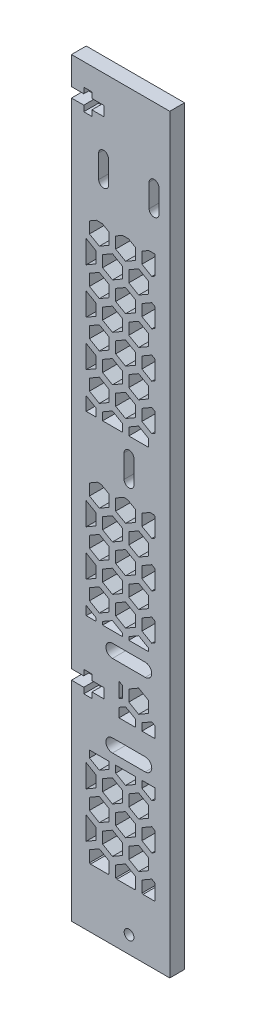
SolidWorks part; units mm, degrees
ref_plane "Front Plane" through (0, 0, 0) normal (0, 0, 1) x (1, 0, 0)
ref_plane "Top Plane" through (0, 0, 0) normal (0, 1, 0) x (1, 0, 0)
ref_plane "Right Plane" through (0, 0, 0) normal (1, 0, 0) x (0, 0, -1)
sketch "Sketch1" plane through (0, 0, 0) normal (0, 0, 1) x (1, 0, 0)
  line B0 (0, 114.5304) -> (25, 114.5304)
  line B1 (0, 114.5304) -> (0, -114.5304)
  line B2 (0, -114.5304) -> (25, -114.5304)
  line B3 (25, 114.5304) -> (25, -114.5304)
  line B4 (3.3, 89.1304) -> (0, 89.1304) construction
  line B5 (21.7, 89.1304) -> (25, 89.1304) construction
  line B6 (0, -100.1081) -> (25, -100.1081) construction
  circle B7 centre (4.8, 89.1304) radius 1.5
  circle B8 centre (20.2, 89.1304) radius 1.5
  circle B9 centre (12.5588, 13.7722) radius 1.5
  spline B10 degree 3 poles (11.075, -109.3281) (11.075, -112.3281) (14.075, -112.3281) (14.075, -109.3281) (14.075, -106.3281) (11.075, -106.3281) (11.075, -109.3281) (11.075, -112.3281) (14.075, -112.3281) knots -0.5 0 0 0 0.5 0.5 0.5 1 1 1 1.5 1.5 1.5 weights 1 0.333333 0.333333 1 0.333333 0.333333 1 0.333333 0.333333 only from (11.075, -109.3281) to (11.075, -109.3281)
sketch_block_instance "Block-sideExtraSupport-1"
sketch_block "Block-sideExtraSupport" parameters "D1"=25
extrude "Boss-Extrude1" add sketch "Sketch1" along normal blind 4.5 contours B1 B6 B3 B0 B9 B8 B7
sketch "Sketch2" plane through (0, 0, 4.5) normal (0, 0, 1) x (1, 0, 0)
  line L1 (0, -114.5304) -> (25, -114.5304) construction
  point P3 (12.5, -114.5304)
  line B0 (0, -24.3132) -> (40.525, -24.3132) construction
  line B1 (0, -24.3132) -> (0, -74.3132) construction
  line B2 (0, -74.3132) -> (40.525, -74.3132) construction
  line B3 (40.525, -24.3132) -> (40.525, -74.3132) construction
  line B4 (32.525, -24.3132) -> (28.125, -24.3132) construction
  line B5 (20.2625, -24.3132) -> (20.2625, -49.3132) construction
  line B6 (20.2625, -49.3132) -> (0, -49.3132) construction
  line B7 (20.2625, -36.8132) -> (0, -36.8132) construction
  line B8 (28.125, -64.3132) -> (32.525, -64.3132) construction
  line B9 (32.525, -64.3132) -> (32.525, -34.3132) construction
  line B10 (28.125, -64.3132) -> (28.125, -34.3132) construction
  line B11 (28.125, -34.3132) -> (32.525, -34.3132) construction
  line B12 (27.625, -64.8132) -> (33.025, -64.8132) construction
  line B13 (33.025, -64.8132) -> (33.025, -33.8132) construction
  line B14 (27.625, -33.8132) -> (33.025, -33.8132) construction
  line B15 (27.625, -64.8132) -> (27.625, -33.8132) construction
  line B16 (0, -100.1081) -> (25, -100.1081) construction
  line B17 (25, -114.5304) -> (0, -114.5304) construction
  line B18 (12.5, -100.1081) -> (12.5, -61.8132) construction
  line B19 (12.5, -114.5304) -> (12.5, -100.1081) construction
  line B20 (7.5, -36.8132) -> (17.5, -36.8132)
  line B21 (7.5, -34.8132) -> (17.5, -34.8132)
  line B22 (7.5, -38.8132) -> (17.5, -38.8132)
  line B23 (7.5, -61.8132) -> (17.5, -61.8132)
  line B24 (7.5, -63.8132) -> (17.5, -63.8132)
  line B25 (7.5, -59.8132) -> (17.5, -59.8132)
  arc B26 (7.5, -34.8132) -> (7.5, -38.8132) centre (7.5, -36.8132) ccw
  arc B27 (17.5, -38.8132) -> (17.5, -34.8132) centre (17.5, -36.8132) ccw
  arc B28 (7.5, -63.8132) -> (7.5, -59.8132) centre (7.5, -61.8132) cw
  arc B29 (17.5, -59.8132) -> (17.5, -63.8132) centre (17.5, -61.8132) cw
sketch_block_instance "Block-SidePanelSketch2-1"
sketch_block "Block-SidePanelSketch2" parameters "D1"=50, "D2"=4, "D3"=10, "D4"=8
extrude "Cut-Extrude1" cut sketch "Sketch2" against normal through all
sketch "Sketch3" plane through (0, 0, 4.5) normal (0, 0, 1) x (1, 0, 0)
  line L0 (12.5, 114.5304) -> (12.5, -114.5304) construction
  line L1 (0, 114.5304) -> (25, 114.5304) construction
  line L2 (0, -114.5304) -> (25, -114.5304) construction
  line L3 (4.8, 92.6304) -> (4.8, 85.6304) construction
  line L4 (6.3, 92.6304) -> (6.3, 85.6304)
  line L5 (3.3, 92.6304) -> (3.3, 85.6304)
  line L6 (20.2, 92.6304) -> (20.2, 85.6304) construction
  line L7 (18.7, 92.6304) -> (18.7, 85.6304)
  line L8 (21.7, 92.6304) -> (21.7, 85.6304)
  line L9 (12.5588, 17.2722) -> (12.5588, 10.2722) construction
  line L10 (14.0588, 17.2722) -> (14.0588, 10.2722)
  line L11 (11.0588, 17.2722) -> (11.0588, 10.2722)
  arc A1 (6.3, 92.6304) -> (3.3, 92.6304) centre (4.8, 92.6304) ccw
  arc A2 (3.3, 85.6304) -> (6.3, 85.6304) centre (4.8, 85.6304) ccw
  circle A3 centre (4.8, 89.1304) radius 1.5 construction
  arc A4 (18.7, 92.6304) -> (21.7, 92.6304) centre (20.2, 92.6304) cw
  arc A5 (21.7, 85.6304) -> (18.7, 85.6304) centre (20.2, 85.6304) cw
  arc A6 (14.0588, 17.2722) -> (11.0588, 17.2722) centre (12.5588, 17.2722) ccw
  arc A7 (11.0588, 10.2722) -> (14.0588, 10.2722) centre (12.5588, 10.2722) ccw
  circle A8 centre (12.5588, 13.7722) radius 1.5 construction
  point P6 (4.8, 89.1304)
  point P10 (12.5588, 18.7722)
  point P14 (12.5588, 13.7722)
  point P19 (4.8, 94.1304)
  point P22 (20.2, 89.1304)
  dimension "D1" = 5
  dimension "D2" = 5
extrude "Cut-Extrude2" cut sketch "Sketch3" against normal through all
sketch "Sketch4" plane through (0, 0, 0) normal (-1, 0, 0) x (0, 0, 1)
  line L1 (0, 114.5304) -> (4.5, 114.5304)
  line L2 (0, 114.5304) -> (0, -114.5304)
  line L3 (0, -114.5304) -> (4.5, -114.5304)
  line L4 (4.5, 114.5304) -> (4.5, -114.5304)
  line L5 (0, 114.5304) -> (4.5, -114.5304) construction
  line L6 (0, -114.5304) -> (4.5, 114.5304) construction
  point P4 (2.25, 0)
extrude "Boss-Extrude2" add sketch "Sketch4" along normal blind 5
sketch "Sketch5" plane through (0, 0, 4.5) normal (0, 0, 1) x (1, 0, 0)
  line L0 (-5, 106.0304) -> (5, 106.0304)
  line L1 (-5, 106.0304) -> (-5, 103.0304)
  line L2 (-5, 103.0304) -> (5, 103.0304)
  line L3 (5, 106.0304) -> (5, 103.0304)
  line L4 (-5, 106.0304) -> (5, 103.0304) construction
  line L5 (-5, 103.0304) -> (5, 106.0304) construction
  line L6 (-5, -47.8132) -> (5, -47.8132)
  line L7 (-5, -47.8132) -> (-5, -50.8132)
  line L8 (-5, -50.8132) -> (5, -50.8132)
  line L9 (5, -47.8132) -> (5, -50.8132)
  line L10 (-5, -47.8132) -> (5, -50.8132) construction
  line L11 (-5, -50.8132) -> (5, -47.8132) construction
  line L12 (-1.25, 107.7804) -> (1.25, 107.7804)
  line L13 (-1.25, 107.7804) -> (-1.25, 101.2804)
  line L14 (-1.25, 101.2804) -> (1.25, 101.2804)
  line L15 (1.25, 107.7804) -> (1.25, 101.2804)
  line L16 (-1.25, 107.7804) -> (1.25, 101.2804) construction
  line L17 (-1.25, 101.2804) -> (1.25, 107.7804) construction
  line L18 (-1.25, -46.0632) -> (1.25, -46.0632)
  line L19 (-1.25, -46.0632) -> (-1.25, -52.5632)
  line L20 (-1.25, -52.5632) -> (1.25, -52.5632)
  line L21 (1.25, -46.0632) -> (1.25, -52.5632)
  line L22 (-1.25, -46.0632) -> (1.25, -52.5632) construction
  line L23 (-1.25, -52.5632) -> (1.25, -46.0632) construction
  line L24 (13.5226, -38.8132) -> (13.5226, -59.8132) construction
  line L25 (-5, -114.5304) -> (-5, 114.5304) construction
  point P4 (0, 104.5304)
  point P9 (0, -49.3132)
  point P10 (0, 104.5304)
  point P15 (0, -49.3132)
  point P22 (13.5226, -49.3132)
  line M25 (-5, 114.5304) -> (-5, -114.5304)
  dimension "D1" = 2.5
  dimension "D2" = 6.5
  dimension "D3" = 3
  dimension "D4" = 10
extrude "Cut-Extrude3" cut sketch "Sketch5" against normal blind 5 contours L19 L6 L8 M25 | L21 L6 L19 L8 | L21 L18 L19 L6 | L6 L21 L8 L9 | L21 L8 L19 L20 | L0 L15 L2 L3 | L15 L2 L13 L14 | L15 L0 L13 L2 | L13 L0 L2 M25 | L15 L12 L13 L0
sketch "Sketch6" plane through (0, 0, 4.5) normal (0, 0, 1) x (1, 0, 0)
  line L0 (25, 114.5304) -> (25, -114.5304) construction
  line L1 (20.5, -96.5304) -> (-0.5, -96.5304)
  line L2 (20.5, -96.5304) -> (20.5, -66.5304)
  line L3 (20.5, -66.5304) -> (-0.5, -66.5304)
  line L4 (-0.5, -96.5304) -> (-0.5, -66.5304)
  line L5 (20.5, -96.5304) -> (-0.5, -66.5304) construction
  line L6 (20.5, -66.5304) -> (-0.5, -96.5304) construction
  line L7 (20.5, -53.5304) -> (9.5, -53.5304)
  line L8 (20.5, -53.5304) -> (20.5, -42.5304)
  line L9 (20.5, -42.5304) -> (9.5, -42.5304)
  line L10 (9.5, -53.5304) -> (9.5, -42.5304)
  line L11 (20.5, -53.5304) -> (9.5, -42.5304) construction
  line L12 (20.5, -42.5304) -> (9.5, -53.5304) construction
  line L13 (20.5, -31.5304) -> (-0.5, -31.5304)
  line L14 (20.5, -31.5304) -> (20.5, 5.4696)
  line L15 (20.5, 5.4696) -> (-0.5, 5.4696)
  line L16 (-0.5, -31.5304) -> (-0.5, 5.4696)
  line L17 (20.5, -31.5304) -> (-0.5, 5.4696) construction
  line L18 (20.5, 5.4696) -> (-0.5, -31.5304) construction
  line L19 (20.5, 22.4696) -> (-0.5, 22.4696)
  line L20 (20.5, 22.4696) -> (20.5, 74.5304)
  line L21 (20.5, 74.5304) -> (-0.5, 74.5304)
  line L22 (-0.5, 22.4696) -> (-0.5, 74.5304)
  line L23 (20.5, 22.4696) -> (-0.5, 74.5304) construction
  line L24 (20.5, 74.5304) -> (-0.5, 22.4696) construction
  line L25 (-5, -114.5304) -> (25, -114.5304) construction
  line L26 (-5, -114.5304) -> (-5, -50.8132) construction
  line L27 (-5, 114.5304) -> (25, 114.5304) construction
  line L28 (10.5, -103.2624) -> (10.5, -99.7983)
  line L29 (2.5, -103.2624) -> (2.5, -99.7983)
  line L30 (2.5, -99.7983) -> (-0.5, -98.0663)
  line L31 (-0.5, -98.0663) -> (-3.5, -99.7983)
  line L32 (-3.5, -99.7983) -> (-3.5, -103.2624)
  line L33 (-3.5, -103.2624) -> (-0.5, -104.9945)
  line L34 (-0.5, -104.9945) -> (2.5, -103.2624)
  line L35 (3.5, -111.9227) -> (6.5, -110.1906)
  line L36 (6.5, -110.1906) -> (6.5, -106.7265)
  line L37 (6.5, -106.7265) -> (3.5, -104.9945)
  line L38 (3.5, -104.9945) -> (0.5, -106.7265)
  line L39 (0.5, -106.7265) -> (0.5, -110.1906)
  line L40 (0.5, -110.1906) -> (3.5, -111.9227)
  line L41 (10.5, -99.7983) -> (7.5, -98.0663)
  line L42 (7.5, -98.0663) -> (4.5, -99.7983)
  line L43 (4.5, -99.7983) -> (4.5, -103.2624)
  line L44 (4.5, -103.2624) -> (7.5, -104.9945)
  line L45 (7.5, -104.9945) -> (10.5, -103.2624)
  line L46 (11.5, -111.9227) -> (14.5, -110.1906)
  line L47 (14.5, -110.1906) -> (14.5, -106.7265)
  line L48 (14.5, -106.7265) -> (11.5, -104.9945)
  line L49 (11.5, -104.9945) -> (8.5, -106.7265)
  line L50 (8.5, -106.7265) -> (8.5, -110.1906)
  line L51 (8.5, -110.1906) -> (11.5, -111.9227)
  line L52 (18.5, -103.2624) -> (18.5, -99.7983)
  line L53 (18.5, -99.7983) -> (15.5, -98.0663)
  line L54 (15.5, -98.0663) -> (12.5, -99.7983)
  line L55 (12.5, -99.7983) -> (12.5, -103.2624)
  line L56 (12.5, -103.2624) -> (15.5, -104.9945)
  line L57 (15.5, -104.9945) -> (18.5, -103.2624)
  line L58 (19.5, -111.9227) -> (22.5, -110.1906)
  line L59 (22.5, -110.1906) -> (22.5, -106.7265)
  line L60 (22.5, -106.7265) -> (19.5, -104.9945)
  line L61 (19.5, -104.9945) -> (16.5, -106.7265)
  line L62 (16.5, -106.7265) -> (16.5, -110.1906)
  line L63 (16.5, -110.1906) -> (19.5, -111.9227)
  line L64 (26.5, -103.2624) -> (26.5, -99.7983)
  line L65 (26.5, -99.7983) -> (23.5, -98.0663)
  line L66 (23.5, -98.0663) -> (20.5, -99.7983)
  line L67 (20.5, -99.7983) -> (20.5, -103.2624)
  line L68 (20.5, -103.2624) -> (23.5, -104.9945)
  line L69 (23.5, -104.9945) -> (26.5, -103.2624)
  line L70 (27.5, -111.9227) -> (30.5, -110.1906)
  line L71 (30.5, -110.1906) -> (30.5, -106.7265)
  line L72 (30.5, -106.7265) -> (27.5, -104.9945)
  line L73 (27.5, -104.9945) -> (24.5, -106.7265)
  line L74 (24.5, -106.7265) -> (24.5, -110.1906)
  line L75 (24.5, -110.1906) -> (27.5, -111.9227)
  line L76 (10.5, -89.4124) -> (10.5, -85.9483)
  line L77 (10.5, -85.9483) -> (7.5, -84.2163)
  line L78 (7.5, -84.2163) -> (4.5, -85.9483)
  line L79 (4.5, -85.9483) -> (4.5, -89.4124)
  line L80 (4.5, -89.4124) -> (7.5, -91.1445)
  line L81 (7.5, -91.1445) -> (10.5, -89.4124)
  line L82 (11.5, -98.0727) -> (14.5, -96.3406)
  line L83 (14.5, -96.3406) -> (14.5, -92.8765)
  line L84 (14.5, -92.8765) -> (11.5, -91.1445)
  line L85 (11.5, -91.1445) -> (8.5, -92.8765)
  line L86 (8.5, -92.8765) -> (8.5, -96.3406)
  line L87 (8.5, -96.3406) -> (11.5, -98.0727)
  line L88 (18.5, -89.4124) -> (18.5, -85.9483)
  line L89 (18.5, -85.9483) -> (15.5, -84.2163)
  line L90 (15.5, -84.2163) -> (12.5, -85.9483)
  line L91 (12.5, -85.9483) -> (12.5, -89.4124)
  line L92 (12.5, -89.4124) -> (15.5, -91.1445)
  line L93 (15.5, -91.1445) -> (18.5, -89.4124)
  line L94 (19.5, -98.0727) -> (22.5, -96.3406)
  line L95 (22.5, -96.3406) -> (22.5, -92.8765)
  line L96 (22.5, -92.8765) -> (19.5, -91.1445)
  line L97 (19.5, -91.1445) -> (16.5, -92.8765)
  line L98 (16.5, -92.8765) -> (16.5, -96.3406)
  line L99 (16.5, -96.3406) -> (19.5, -98.0727)
  line L100 (26.5, -89.4124) -> (26.5, -85.9483)
  line L101 (26.5, -85.9483) -> (23.5, -84.2163)
  line L102 (23.5, -84.2163) -> (20.5, -85.9483)
  line L103 (20.5, -85.9483) -> (20.5, -89.4124)
  line L104 (20.5, -89.4124) -> (23.5, -91.1445)
  line L105 (23.5, -91.1445) -> (26.5, -89.4124)
  line L106 (27.5, -98.0727) -> (30.5, -96.3406)
  line L107 (30.5, -96.3406) -> (30.5, -92.8765)
  line L108 (30.5, -92.8765) -> (27.5, -91.1445)
  line L109 (27.5, -91.1445) -> (24.5, -92.8765)
  line L110 (24.5, -92.8765) -> (24.5, -96.3406)
  line L111 (24.5, -96.3406) -> (27.5, -98.0727)
  line L112 (10.5, -75.5624) -> (10.5, -72.0983)
  line L113 (10.5, -72.0983) -> (7.5, -70.3663)
  line L114 (7.5, -70.3663) -> (4.5, -72.0983)
  line L115 (4.5, -72.0983) -> (4.5, -75.5624)
  line L116 (4.5, -75.5624) -> (7.5, -77.2945)
  line L117 (7.5, -77.2945) -> (10.5, -75.5624)
  line L118 (11.5, -84.2227) -> (14.5, -82.4906)
  line L119 (14.5, -82.4906) -> (14.5, -79.0265)
  line L120 (14.5, -79.0265) -> (11.5, -77.2945)
  line L121 (11.5, -77.2945) -> (8.5, -79.0265)
  line L122 (8.5, -79.0265) -> (8.5, -82.4906)
  line L123 (8.5, -82.4906) -> (11.5, -84.2227)
  line L124 (18.5, -75.5624) -> (18.5, -72.0983)
  line L125 (18.5, -72.0983) -> (15.5, -70.3663)
  line L126 (15.5, -70.3663) -> (12.5, -72.0983)
  line L127 (12.5, -72.0983) -> (12.5, -75.5624)
  line L128 (12.5, -75.5624) -> (15.5, -77.2945)
  line L129 (15.5, -77.2945) -> (18.5, -75.5624)
  line L130 (19.5, -84.2227) -> (22.5, -82.4906)
  line L131 (22.5, -82.4906) -> (22.5, -79.0265)
  line L132 (22.5, -79.0265) -> (19.5, -77.2945)
  line L133 (19.5, -77.2945) -> (16.5, -79.0265)
  line L134 (16.5, -79.0265) -> (16.5, -82.4906)
  line L135 (16.5, -82.4906) -> (19.5, -84.2227)
  line L136 (26.5, -75.5624) -> (26.5, -72.0983)
  line L137 (26.5, -72.0983) -> (23.5, -70.3663)
  line L138 (23.5, -70.3663) -> (20.5, -72.0983)
  line L139 (20.5, -72.0983) -> (20.5, -75.5624)
  line L140 (20.5, -75.5624) -> (23.5, -77.2945)
  line L141 (23.5, -77.2945) -> (26.5, -75.5624)
  line L142 (27.5, -84.2227) -> (30.5, -82.4906)
  line L143 (30.5, -82.4906) -> (30.5, -79.0265)
  line L144 (30.5, -79.0265) -> (27.5, -77.2945)
  line L145 (27.5, -77.2945) -> (24.5, -79.0265)
  line L146 (24.5, -79.0265) -> (24.5, -82.4906)
  line L147 (24.5, -82.4906) -> (27.5, -84.2227)
  line L154 (11.5, -70.3727) -> (14.5, -68.6406)
  line L155 (14.5, -68.6406) -> (14.5, -65.1765)
  line L156 (14.5, -65.1765) -> (11.5, -63.4445)
  line L157 (11.5, -63.4445) -> (8.5, -65.1765)
  line L158 (8.5, -65.1765) -> (8.5, -68.6406)
  line L159 (8.5, -68.6406) -> (11.5, -70.3727)
  line L166 (19.5, -70.3727) -> (22.5, -68.6406)
  line L167 (22.5, -68.6406) -> (22.5, -65.1765)
  line L168 (22.5, -65.1765) -> (19.5, -63.4445)
  line L169 (19.5, -63.4445) -> (16.5, -65.1765)
  line L170 (16.5, -65.1765) -> (16.5, -68.6406)
  line L171 (16.5, -68.6406) -> (19.5, -70.3727)
  line L178 (27.5, -70.3727) -> (30.5, -68.6406)
  line L179 (30.5, -68.6406) -> (30.5, -65.1765)
  line L180 (30.5, -65.1765) -> (27.5, -63.4445)
  line L181 (27.5, -63.4445) -> (24.5, -65.1765)
  line L182 (24.5, -65.1765) -> (24.5, -68.6406)
  line L183 (24.5, -68.6406) -> (27.5, -70.3727)
  line L184 (10.5, -47.8624) -> (10.5, -44.3983)
  line L185 (10.5, -44.3983) -> (7.5, -42.6663)
  line L186 (7.5, -42.6663) -> (4.5, -44.3983)
  line L187 (4.5, -44.3983) -> (4.5, -47.8624)
  line L188 (4.5, -47.8624) -> (7.5, -49.5945)
  line L189 (7.5, -49.5945) -> (10.5, -47.8624)
  line L190 (11.5, -56.5227) -> (14.5, -54.7906)
  line L191 (14.5, -54.7906) -> (14.5, -51.3265)
  line L192 (14.5, -51.3265) -> (11.5, -49.5945)
  line L193 (11.5, -49.5945) -> (8.5, -51.3265)
  line L194 (8.5, -51.3265) -> (8.5, -54.7906)
  line L195 (8.5, -54.7906) -> (11.5, -56.5227)
  line L196 (18.5, -47.8624) -> (18.5, -44.3983)
  line L197 (18.5, -44.3983) -> (15.5, -42.6663)
  line L198 (15.5, -42.6663) -> (12.5, -44.3983)
  line L199 (12.5, -44.3983) -> (12.5, -47.8624)
  line L200 (12.5, -47.8624) -> (15.5, -49.5945)
  line L201 (15.5, -49.5945) -> (18.5, -47.8624)
  line L202 (19.5, -56.5227) -> (22.5, -54.7906)
  line L203 (22.5, -54.7906) -> (22.5, -51.3265)
  line L204 (22.5, -51.3265) -> (19.5, -49.5945)
  line L205 (19.5, -49.5945) -> (16.5, -51.3265)
  line L206 (16.5, -51.3265) -> (16.5, -54.7906)
  line L207 (16.5, -54.7906) -> (19.5, -56.5227)
  line L208 (26.5, -47.8624) -> (26.5, -44.3983)
  line L209 (26.5, -44.3983) -> (23.5, -42.6663)
  line L210 (23.5, -42.6663) -> (20.5, -44.3983)
  line L211 (20.5, -44.3983) -> (20.5, -47.8624)
  line L212 (20.5, -47.8624) -> (23.5, -49.5945)
  line L213 (23.5, -49.5945) -> (26.5, -47.8624)
  line L214 (27.5, -56.5227) -> (30.5, -54.7906)
  line L215 (30.5, -54.7906) -> (30.5, -51.3265)
  line L216 (30.5, -51.3265) -> (27.5, -49.5945)
  line L217 (27.5, -49.5945) -> (24.5, -51.3265)
  line L218 (24.5, -51.3265) -> (24.5, -54.7906)
  line L219 (24.5, -54.7906) -> (27.5, -56.5227)
  line L220 (10.5, -34.0124) -> (10.5, -30.5483)
  line L221 (10.5, -30.5483) -> (7.5, -28.8163)
  line L222 (7.5, -28.8163) -> (4.5, -30.5483)
  line L223 (4.5, -30.5483) -> (4.5, -34.0124)
  line L224 (4.5, -34.0124) -> (7.5, -35.7445)
  line L225 (7.5, -35.7445) -> (10.5, -34.0124)
  line L226 (11.5, -42.6727) -> (14.5, -40.9406)
  line L227 (14.5, -40.9406) -> (14.5, -37.4765)
  line L228 (14.5, -37.4765) -> (11.5, -35.7445)
  line L229 (11.5, -35.7445) -> (8.5, -37.4765)
  line L230 (8.5, -37.4765) -> (8.5, -40.9406)
  line L231 (8.5, -40.9406) -> (11.5, -42.6727)
  line L232 (18.5, -34.0124) -> (18.5, -30.5483)
  line L233 (18.5, -30.5483) -> (15.5, -28.8163)
  line L234 (15.5, -28.8163) -> (12.5, -30.5483)
  line L235 (12.5, -30.5483) -> (12.5, -34.0124)
  line L236 (12.5, -34.0124) -> (15.5, -35.7445)
  line L237 (15.5, -35.7445) -> (18.5, -34.0124)
  line L238 (19.5, -42.6727) -> (22.5, -40.9406)
  line L239 (22.5, -40.9406) -> (22.5, -37.4765)
  line L240 (22.5, -37.4765) -> (19.5, -35.7445)
  line L241 (19.5, -35.7445) -> (16.5, -37.4765)
  line L242 (16.5, -37.4765) -> (16.5, -40.9406)
  line L243 (16.5, -40.9406) -> (19.5, -42.6727)
  line L244 (26.5, -34.0124) -> (26.5, -30.5483)
  line L245 (26.5, -30.5483) -> (23.5, -28.8163)
  line L246 (23.5, -28.8163) -> (20.5, -30.5483)
  line L247 (20.5, -30.5483) -> (20.5, -34.0124)
  line L248 (20.5, -34.0124) -> (23.5, -35.7445)
  line L249 (23.5, -35.7445) -> (26.5, -34.0124)
  line L250 (27.5, -42.6727) -> (30.5, -40.9406)
  line L251 (30.5, -40.9406) -> (30.5, -37.4765)
  line L252 (30.5, -37.4765) -> (27.5, -35.7445)
  line L253 (27.5, -35.7445) -> (24.5, -37.4765)
  line L254 (24.5, -37.4765) -> (24.5, -40.9406)
  line L255 (24.5, -40.9406) -> (27.5, -42.6727)
  line L256 (10.5, -20.1624) -> (10.5, -16.6983)
  line L257 (10.5, -16.6983) -> (7.5, -14.9663)
  line L258 (7.5, -14.9663) -> (4.5, -16.6983)
  line L259 (4.5, -16.6983) -> (4.5, -20.1624)
  line L260 (4.5, -20.1624) -> (7.5, -21.8945)
  line L261 (7.5, -21.8945) -> (10.5, -20.1624)
  line L262 (11.5, -28.8227) -> (14.5, -27.0906)
  line L263 (14.5, -27.0906) -> (14.5, -23.6265)
  line L264 (14.5, -23.6265) -> (11.5, -21.8945)
  line L265 (11.5, -21.8945) -> (8.5, -23.6265)
  line L266 (8.5, -23.6265) -> (8.5, -27.0906)
  line L267 (8.5, -27.0906) -> (11.5, -28.8227)
  line L268 (18.5, -20.1624) -> (18.5, -16.6983)
  line L269 (18.5, -16.6983) -> (15.5, -14.9663)
  line L270 (15.5, -14.9663) -> (12.5, -16.6983)
  line L271 (12.5, -16.6983) -> (12.5, -20.1624)
  line L272 (12.5, -20.1624) -> (15.5, -21.8945)
  line L273 (15.5, -21.8945) -> (18.5, -20.1624)
  line L274 (19.5, -28.8227) -> (22.5, -27.0906)
  line L275 (22.5, -27.0906) -> (22.5, -23.6265)
  line L276 (22.5, -23.6265) -> (19.5, -21.8945)
  line L277 (19.5, -21.8945) -> (16.5, -23.6265)
  line L278 (16.5, -23.6265) -> (16.5, -27.0906)
  line L279 (16.5, -27.0906) -> (19.5, -28.8227)
  line L280 (26.5, -20.1624) -> (26.5, -16.6983)
  line L281 (26.5, -16.6983) -> (23.5, -14.9663)
  line L282 (23.5, -14.9663) -> (20.5, -16.6983)
  line L283 (20.5, -16.6983) -> (20.5, -20.1624)
  line L284 (20.5, -20.1624) -> (23.5, -21.8945)
  line L285 (23.5, -21.8945) -> (26.5, -20.1624)
  line L286 (27.5, -28.8227) -> (30.5, -27.0906)
  line L287 (30.5, -27.0906) -> (30.5, -23.6265)
  line L288 (30.5, -23.6265) -> (27.5, -21.8945)
  line L289 (27.5, -21.8945) -> (24.5, -23.6265)
  line L290 (24.5, -23.6265) -> (24.5, -27.0906)
  line L291 (24.5, -27.0906) -> (27.5, -28.8227)
  line L292 (10.5, -6.3124) -> (10.5, -2.8483)
  line L293 (10.5, -2.8483) -> (7.5, -1.1163)
  line L294 (7.5, -1.1163) -> (4.5, -2.8483)
  line L295 (4.5, -2.8483) -> (4.5, -6.3124)
  line L296 (4.5, -6.3124) -> (7.5, -8.0445)
  line L297 (7.5, -8.0445) -> (10.5, -6.3124)
  line L298 (11.5, -14.9727) -> (14.5, -13.2406)
  line L299 (14.5, -13.2406) -> (14.5, -9.7765)
  line L300 (14.5, -9.7765) -> (11.5, -8.0445)
  line L301 (11.5, -8.0445) -> (8.5, -9.7765)
  line L302 (8.5, -9.7765) -> (8.5, -13.2406)
  line L303 (8.5, -13.2406) -> (11.5, -14.9727)
  line L304 (18.5, -6.3124) -> (18.5, -2.8483)
  line L305 (18.5, -2.8483) -> (15.5, -1.1163)
  line L306 (15.5, -1.1163) -> (12.5, -2.8483)
  line L307 (12.5, -2.8483) -> (12.5, -6.3124)
  line L308 (12.5, -6.3124) -> (15.5, -8.0445)
  line L309 (15.5, -8.0445) -> (18.5, -6.3124)
  line L310 (19.5, -14.9727) -> (22.5, -13.2406)
  line L311 (22.5, -13.2406) -> (22.5, -9.7765)
  line L312 (22.5, -9.7765) -> (19.5, -8.0445)
  line L313 (19.5, -8.0445) -> (16.5, -9.7765)
  line L314 (16.5, -9.7765) -> (16.5, -13.2406)
  line L315 (16.5, -13.2406) -> (19.5, -14.9727)
  line L316 (26.5, -6.3124) -> (26.5, -2.8483)
  line L317 (26.5, -2.8483) -> (23.5, -1.1163)
  line L318 (23.5, -1.1163) -> (20.5, -2.8483)
  line L319 (20.5, -2.8483) -> (20.5, -6.3124)
  line L320 (20.5, -6.3124) -> (23.5, -8.0445)
  line L321 (23.5, -8.0445) -> (26.5, -6.3124)
  line L322 (27.5, -14.9727) -> (30.5, -13.2406)
  line L323 (30.5, -13.2406) -> (30.5, -9.7765)
  line L324 (30.5, -9.7765) -> (27.5, -8.0445)
  line L325 (27.5, -8.0445) -> (24.5, -9.7765)
  line L326 (24.5, -9.7765) -> (24.5, -13.2406)
  line L327 (24.5, -13.2406) -> (27.5, -14.9727)
  line L328 (10.5, 7.5376) -> (10.5, 11.0017)
  line L329 (10.5, 11.0017) -> (7.5, 12.7337)
  line L330 (7.5, 12.7337) -> (4.5, 11.0017)
  line L331 (4.5, 11.0017) -> (4.5, 7.5376)
  line L332 (4.5, 7.5376) -> (7.5, 5.8055)
  line L333 (7.5, 5.8055) -> (10.5, 7.5376)
  line L334 (11.5, -1.1227) -> (14.5, 0.6094)
  line L335 (14.5, 0.6094) -> (14.5, 4.0735)
  line L336 (14.5, 4.0735) -> (11.5, 5.8055)
  line L337 (11.5, 5.8055) -> (8.5, 4.0735)
  line L338 (8.5, 4.0735) -> (8.5, 0.6094)
  line L339 (8.5, 0.6094) -> (11.5, -1.1227)
  line L340 (18.5, 7.5376) -> (18.5, 11.0017)
  line L341 (18.5, 11.0017) -> (15.5, 12.7337)
  line L342 (15.5, 12.7337) -> (12.5, 11.0017)
  line L343 (12.5, 11.0017) -> (12.5, 7.5376)
  line L344 (12.5, 7.5376) -> (15.5, 5.8055)
  line L345 (15.5, 5.8055) -> (18.5, 7.5376)
  line L346 (19.5, -1.1227) -> (22.5, 0.6094)
  line L347 (22.5, 0.6094) -> (22.5, 4.0735)
  line L348 (22.5, 4.0735) -> (19.5, 5.8055)
  line L349 (19.5, 5.8055) -> (16.5, 4.0735)
  line L350 (16.5, 4.0735) -> (16.5, 0.6094)
  line L351 (16.5, 0.6094) -> (19.5, -1.1227)
  line L352 (26.5, 7.5376) -> (26.5, 11.0017)
  line L353 (26.5, 11.0017) -> (23.5, 12.7337)
  line L354 (23.5, 12.7337) -> (20.5, 11.0017)
  line L355 (20.5, 11.0017) -> (20.5, 7.5376)
  line L356 (20.5, 7.5376) -> (23.5, 5.8055)
  line L357 (23.5, 5.8055) -> (26.5, 7.5376)
  line L358 (27.5, -1.1227) -> (30.5, 0.6094)
  line L359 (30.5, 0.6094) -> (30.5, 4.0735)
  line L360 (30.5, 4.0735) -> (27.5, 5.8055)
  line L361 (27.5, 5.8055) -> (24.5, 4.0735)
  line L362 (24.5, 4.0735) -> (24.5, 0.6094)
  line L363 (24.5, 0.6094) -> (27.5, -1.1227)
  line L364 (10.5, 21.3876) -> (10.5, 24.8517)
  line L365 (10.5, 24.8517) -> (7.5, 26.5837)
  line L366 (7.5, 26.5837) -> (4.5, 24.8517)
  line L367 (4.5, 24.8517) -> (4.5, 21.3876)
  line L368 (4.5, 21.3876) -> (7.5, 19.6555)
  line L369 (7.5, 19.6555) -> (10.5, 21.3876)
  line L370 (11.5, 12.7273) -> (14.5, 14.4594)
  line L371 (14.5, 14.4594) -> (14.5, 17.9235)
  line L372 (14.5, 17.9235) -> (11.5, 19.6555)
  line L373 (11.5, 19.6555) -> (8.5, 17.9235)
  line L374 (8.5, 17.9235) -> (8.5, 14.4594)
  line L375 (8.5, 14.4594) -> (11.5, 12.7273)
  line L376 (18.5, 21.3876) -> (18.5, 24.8517)
  line L377 (18.5, 24.8517) -> (15.5, 26.5837)
  line L378 (15.5, 26.5837) -> (12.5, 24.8517)
  line L379 (12.5, 24.8517) -> (12.5, 21.3876)
  line L380 (12.5, 21.3876) -> (15.5, 19.6555)
  line L381 (15.5, 19.6555) -> (18.5, 21.3876)
  line L382 (19.5, 12.7273) -> (22.5, 14.4594)
  line L383 (22.5, 14.4594) -> (22.5, 17.9235)
  line L384 (22.5, 17.9235) -> (19.5, 19.6555)
  line L385 (19.5, 19.6555) -> (16.5, 17.9235)
  line L386 (16.5, 17.9235) -> (16.5, 14.4594)
  line L387 (16.5, 14.4594) -> (19.5, 12.7273)
  line L388 (26.5, 21.3876) -> (26.5, 24.8517)
  line L389 (26.5, 24.8517) -> (23.5, 26.5837)
  line L390 (23.5, 26.5837) -> (20.5, 24.8517)
  line L391 (20.5, 24.8517) -> (20.5, 21.3876)
  line L392 (20.5, 21.3876) -> (23.5, 19.6555)
  line L393 (23.5, 19.6555) -> (26.5, 21.3876)
  line L394 (27.5, 12.7273) -> (30.5, 14.4594)
  line L395 (30.5, 14.4594) -> (30.5, 17.9235)
  line L396 (30.5, 17.9235) -> (27.5, 19.6555)
  line L397 (27.5, 19.6555) -> (24.5, 17.9235)
  line L398 (24.5, 17.9235) -> (24.5, 14.4594)
  line L399 (24.5, 14.4594) -> (27.5, 12.7273)
  line L400 (10.5, 35.2376) -> (10.5, 38.7017)
  line L401 (10.5, 38.7017) -> (7.5, 40.4337)
  line L402 (7.5, 40.4337) -> (4.5, 38.7017)
  line L403 (4.5, 38.7017) -> (4.5, 35.2376)
  line L404 (4.5, 35.2376) -> (7.5, 33.5055)
  line L405 (7.5, 33.5055) -> (10.5, 35.2376)
  line L406 (11.5, 26.5773) -> (14.5, 28.3094)
  line L407 (14.5, 28.3094) -> (14.5, 31.7735)
  line L408 (14.5, 31.7735) -> (11.5, 33.5055)
  line L409 (11.5, 33.5055) -> (8.5, 31.7735)
  line L410 (8.5, 31.7735) -> (8.5, 28.3094)
  line L411 (8.5, 28.3094) -> (11.5, 26.5773)
  line L412 (18.5, 35.2376) -> (18.5, 38.7017)
  line L413 (18.5, 38.7017) -> (15.5, 40.4337)
  line L414 (15.5, 40.4337) -> (12.5, 38.7017)
  line L415 (12.5, 38.7017) -> (12.5, 35.2376)
  line L416 (12.5, 35.2376) -> (15.5, 33.5055)
  line L417 (15.5, 33.5055) -> (18.5, 35.2376)
  line L418 (19.5, 26.5773) -> (22.5, 28.3094)
  line L419 (22.5, 28.3094) -> (22.5, 31.7735)
  line L420 (22.5, 31.7735) -> (19.5, 33.5055)
  line L421 (19.5, 33.5055) -> (16.5, 31.7735)
  line L422 (16.5, 31.7735) -> (16.5, 28.3094)
  line L423 (16.5, 28.3094) -> (19.5, 26.5773)
  line L424 (26.5, 35.2376) -> (26.5, 38.7017)
  line L425 (26.5, 38.7017) -> (23.5, 40.4337)
  line L426 (23.5, 40.4337) -> (20.5, 38.7017)
  line L427 (20.5, 38.7017) -> (20.5, 35.2376)
  line L428 (20.5, 35.2376) -> (23.5, 33.5055)
  line L429 (23.5, 33.5055) -> (26.5, 35.2376)
  line L430 (27.5, 26.5773) -> (30.5, 28.3094)
  line L431 (30.5, 28.3094) -> (30.5, 31.7735)
  line L432 (30.5, 31.7735) -> (27.5, 33.5055)
  line L433 (27.5, 33.5055) -> (24.5, 31.7735)
  line L434 (24.5, 31.7735) -> (24.5, 28.3094)
  line L435 (24.5, 28.3094) -> (27.5, 26.5773)
  line L436 (10.5, 49.0876) -> (10.5, 52.5517)
  line L437 (10.5, 52.5517) -> (7.5, 54.2837)
  line L438 (7.5, 54.2837) -> (4.5, 52.5517)
  line L439 (4.5, 52.5517) -> (4.5, 49.0876)
  line L440 (4.5, 49.0876) -> (7.5, 47.3555)
  line L441 (7.5, 47.3555) -> (10.5, 49.0876)
  line L442 (11.5, 40.4273) -> (14.5, 42.1594)
  line L443 (14.5, 42.1594) -> (14.5, 45.6235)
  line L444 (14.5, 45.6235) -> (11.5, 47.3555)
  line L445 (11.5, 47.3555) -> (8.5, 45.6235)
  line L446 (8.5, 45.6235) -> (8.5, 42.1594)
  line L447 (8.5, 42.1594) -> (11.5, 40.4273)
  line L448 (18.5, 49.0876) -> (18.5, 52.5517)
  line L449 (18.5, 52.5517) -> (15.5, 54.2837)
  line L450 (15.5, 54.2837) -> (12.5, 52.5517)
  line L451 (12.5, 52.5517) -> (12.5, 49.0876)
  line L452 (12.5, 49.0876) -> (15.5, 47.3555)
  line L453 (15.5, 47.3555) -> (18.5, 49.0876)
  line L454 (19.5, 40.4273) -> (22.5, 42.1594)
  line L455 (22.5, 42.1594) -> (22.5, 45.6235)
  line L456 (22.5, 45.6235) -> (19.5, 47.3555)
  line L457 (19.5, 47.3555) -> (16.5, 45.6235)
  line L458 (16.5, 45.6235) -> (16.5, 42.1594)
  line L459 (16.5, 42.1594) -> (19.5, 40.4273)
  line L460 (26.5, 49.0876) -> (26.5, 52.5517)
  line L461 (26.5, 52.5517) -> (23.5, 54.2837)
  line L462 (23.5, 54.2837) -> (20.5, 52.5517)
  line L463 (20.5, 52.5517) -> (20.5, 49.0876)
  line L464 (20.5, 49.0876) -> (23.5, 47.3555)
  line L465 (23.5, 47.3555) -> (26.5, 49.0876)
  line L466 (27.5, 40.4273) -> (30.5, 42.1594)
  line L467 (30.5, 42.1594) -> (30.5, 45.6235)
  line L468 (30.5, 45.6235) -> (27.5, 47.3555)
  line L469 (27.5, 47.3555) -> (24.5, 45.6235)
  line L470 (24.5, 45.6235) -> (24.5, 42.1594)
  line L471 (24.5, 42.1594) -> (27.5, 40.4273)
  line L472 (10.5, 62.9376) -> (10.5, 66.4017)
  line L473 (10.5, 66.4017) -> (7.5, 68.1337)
  line L474 (7.5, 68.1337) -> (4.5, 66.4017)
  line L475 (4.5, 66.4017) -> (4.5, 62.9376)
  line L476 (4.5, 62.9376) -> (7.5, 61.2055)
  line L477 (7.5, 61.2055) -> (10.5, 62.9376)
  line L478 (11.5, 54.2773) -> (14.5, 56.0094)
  line L479 (14.5, 56.0094) -> (14.5, 59.4735)
  line L480 (14.5, 59.4735) -> (11.5, 61.2055)
  line L481 (11.5, 61.2055) -> (8.5, 59.4735)
  line L482 (8.5, 59.4735) -> (8.5, 56.0094)
  line L483 (8.5, 56.0094) -> (11.5, 54.2773)
  line L484 (18.5, 62.9376) -> (18.5, 66.4017)
  line L485 (18.5, 66.4017) -> (15.5, 68.1337)
  line L486 (15.5, 68.1337) -> (12.5, 66.4017)
  line L487 (12.5, 66.4017) -> (12.5, 62.9376)
  line L488 (12.5, 62.9376) -> (15.5, 61.2055)
  line L489 (15.5, 61.2055) -> (18.5, 62.9376)
  line L490 (19.5, 54.2773) -> (22.5, 56.0094)
  line L491 (22.5, 56.0094) -> (22.5, 59.4735)
  line L492 (22.5, 59.4735) -> (19.5, 61.2055)
  line L493 (19.5, 61.2055) -> (16.5, 59.4735)
  line L494 (16.5, 59.4735) -> (16.5, 56.0094)
  line L495 (16.5, 56.0094) -> (19.5, 54.2773)
  line L496 (26.5, 62.9376) -> (26.5, 66.4017)
  line L497 (26.5, 66.4017) -> (23.5, 68.1337)
  line L498 (23.5, 68.1337) -> (20.5, 66.4017)
  line L499 (20.5, 66.4017) -> (20.5, 62.9376)
  line L500 (20.5, 62.9376) -> (23.5, 61.2055)
  line L501 (23.5, 61.2055) -> (26.5, 62.9376)
  line L502 (27.5, 54.2773) -> (30.5, 56.0094)
  line L503 (30.5, 56.0094) -> (30.5, 59.4735)
  line L504 (30.5, 59.4735) -> (27.5, 61.2055)
  line L505 (27.5, 61.2055) -> (24.5, 59.4735)
  line L506 (24.5, 59.4735) -> (24.5, 56.0094)
  line L507 (24.5, 56.0094) -> (27.5, 54.2773)
  line L508 (10.5, 76.7876) -> (10.5, 80.2517)
  line L509 (10.5, 80.2517) -> (7.5, 81.9837)
  line L510 (7.5, 81.9837) -> (4.5, 80.2517)
  line L511 (4.5, 80.2517) -> (4.5, 76.7876)
  line L512 (4.5, 76.7876) -> (7.5, 75.0555)
  line L513 (7.5, 75.0555) -> (10.5, 76.7876)
  line L514 (11.5, 68.1273) -> (14.5, 69.8594)
  line L515 (14.5, 69.8594) -> (14.5, 73.3235)
  line L516 (14.5, 73.3235) -> (11.5, 75.0555)
  line L517 (11.5, 75.0555) -> (8.5, 73.3235)
  line L518 (8.5, 73.3235) -> (8.5, 69.8594)
  line L519 (8.5, 69.8594) -> (11.5, 68.1273)
  line L520 (18.5, 76.7876) -> (18.5, 80.2517)
  line L521 (18.5, 80.2517) -> (15.5, 81.9837)
  line L522 (15.5, 81.9837) -> (12.5, 80.2517)
  line L523 (12.5, 80.2517) -> (12.5, 76.7876)
  line L524 (12.5, 76.7876) -> (15.5, 75.0555)
  line L525 (15.5, 75.0555) -> (18.5, 76.7876)
  line L526 (19.5, 68.1273) -> (22.5, 69.8594)
  line L527 (22.5, 69.8594) -> (22.5, 73.3235)
  line L528 (22.5, 73.3235) -> (19.5, 75.0555)
  line L529 (19.5, 75.0555) -> (16.5, 73.3235)
  line L530 (16.5, 73.3235) -> (16.5, 69.8594)
  line L531 (16.5, 69.8594) -> (19.5, 68.1273)
  line L532 (26.5, 76.7876) -> (26.5, 80.2517)
  line L533 (26.5, 80.2517) -> (23.5, 81.9837)
  line L534 (23.5, 81.9837) -> (20.5, 80.2517)
  line L535 (20.5, 80.2517) -> (20.5, 76.7876)
  line L536 (20.5, 76.7876) -> (23.5, 75.0555)
  line L537 (23.5, 75.0555) -> (26.5, 76.7876)
  line L538 (27.5, 68.1273) -> (30.5, 69.8594)
  line L539 (30.5, 69.8594) -> (30.5, 73.3235)
  line L540 (30.5, 73.3235) -> (27.5, 75.0555)
  line L541 (27.5, 75.0555) -> (24.5, 73.3235)
  line L542 (24.5, 73.3235) -> (24.5, 69.8594)
  line L543 (24.5, 69.8594) -> (27.5, 68.1273)
  line L544 (10.5, 90.6376) -> (10.5, 94.1017)
  line L545 (10.5, 94.1017) -> (7.5, 95.8337)
  line L546 (7.5, 95.8337) -> (4.5, 94.1017)
  line L547 (4.5, 94.1017) -> (4.5, 90.6376)
  line L548 (4.5, 90.6376) -> (7.5, 88.9055)
  line L549 (7.5, 88.9055) -> (10.5, 90.6376)
  line L550 (11.5, 81.9773) -> (14.5, 83.7094)
  line L551 (14.5, 83.7094) -> (14.5, 87.1735)
  line L552 (14.5, 87.1735) -> (11.5, 88.9055)
  line L553 (11.5, 88.9055) -> (8.5, 87.1735)
  line L554 (8.5, 87.1735) -> (8.5, 83.7094)
  line L555 (8.5, 83.7094) -> (11.5, 81.9773)
  line L556 (18.5, 90.6376) -> (18.5, 94.1017)
  line L557 (18.5, 94.1017) -> (15.5, 95.8337)
  line L558 (15.5, 95.8337) -> (12.5, 94.1017)
  line L559 (12.5, 94.1017) -> (12.5, 90.6376)
  line L560 (12.5, 90.6376) -> (15.5, 88.9055)
  line L561 (15.5, 88.9055) -> (18.5, 90.6376)
  line L562 (19.5, 81.9773) -> (22.5, 83.7094)
  line L563 (22.5, 83.7094) -> (22.5, 87.1735)
  line L564 (22.5, 87.1735) -> (19.5, 88.9055)
  line L565 (19.5, 88.9055) -> (16.5, 87.1735)
  line L566 (16.5, 87.1735) -> (16.5, 83.7094)
  line L567 (16.5, 83.7094) -> (19.5, 81.9773)
  line L568 (26.5, 90.6376) -> (26.5, 94.1017)
  line L569 (26.5, 94.1017) -> (23.5, 95.8337)
  line L570 (23.5, 95.8337) -> (20.5, 94.1017)
  line L571 (20.5, 94.1017) -> (20.5, 90.6376)
  line L572 (20.5, 90.6376) -> (23.5, 88.9055)
  line L573 (23.5, 88.9055) -> (26.5, 90.6376)
  line L574 (27.5, 81.9773) -> (30.5, 83.7094)
  line L575 (30.5, 83.7094) -> (30.5, 87.1735)
  line L576 (30.5, 87.1735) -> (27.5, 88.9055)
  line L577 (27.5, 88.9055) -> (24.5, 87.1735)
  line L578 (24.5, 87.1735) -> (24.5, 83.7094)
  line L579 (24.5, 83.7094) -> (27.5, 81.9773)
  line L580 (2.5, -89.4124) -> (2.5, -85.9483)
  line L581 (2.5, -85.9483) -> (-0.5, -84.2163)
  line L582 (-0.5, -84.2163) -> (-3.5, -85.9483)
  line L583 (-3.5, -85.9483) -> (-3.5, -89.4124)
  line L584 (-3.5, -89.4124) -> (-0.5, -91.1445)
  line L585 (-0.5, -91.1445) -> (2.5, -89.4124)
  line L586 (3.5, -98.0727) -> (6.5, -96.3406)
  line L587 (6.5, -96.3406) -> (6.5, -92.8765)
  line L588 (6.5, -92.8765) -> (3.5, -91.1445)
  line L589 (3.5, -91.1445) -> (0.5, -92.8765)
  line L590 (0.5, -92.8765) -> (0.5, -96.3406)
  line L591 (0.5, -96.3406) -> (3.5, -98.0727)
  line L592 (2.5, -75.5624) -> (2.5, -72.0983)
  line L593 (2.5, -72.0983) -> (-0.5, -70.3663)
  line L594 (-0.5, -70.3663) -> (-3.5, -72.0983)
  line L595 (-3.5, -72.0983) -> (-3.5, -75.5624)
  line L596 (-3.5, -75.5624) -> (-0.5, -77.2945)
  line L597 (-0.5, -77.2945) -> (2.5, -75.5624)
  line L598 (3.5, -84.2227) -> (6.5, -82.4906)
  line L599 (6.5, -82.4906) -> (6.5, -79.0265)
  line L600 (6.5, -79.0265) -> (3.5, -77.2945)
  line L601 (3.5, -77.2945) -> (0.5, -79.0265)
  line L602 (0.5, -79.0265) -> (0.5, -82.4906)
  line L603 (0.5, -82.4906) -> (3.5, -84.2227)
  line L610 (3.5, -70.3727) -> (6.5, -68.6406)
  line L611 (6.5, -68.6406) -> (6.5, -65.1765)
  line L612 (6.5, -65.1765) -> (3.5, -63.4445)
  line L613 (3.5, -63.4445) -> (0.5, -65.1765)
  line L614 (0.5, -65.1765) -> (0.5, -68.6406)
  line L615 (0.5, -68.6406) -> (3.5, -70.3727)
  line L628 (2.5, -34.0124) -> (2.5, -30.5483)
  line L629 (2.5, -30.5483) -> (-0.5, -28.8163)
  line L630 (-0.5, -28.8163) -> (-3.5, -30.5483)
  line L631 (-3.5, -30.5483) -> (-3.5, -34.0124)
  line L632 (-3.5, -34.0124) -> (-0.5, -35.7445)
  line L633 (-0.5, -35.7445) -> (2.5, -34.0124)
  line L640 (2.5, -20.1624) -> (2.5, -16.6983)
  line L641 (2.5, -16.6983) -> (-0.5, -14.9663)
  line L642 (-0.5, -14.9663) -> (-3.5, -16.6983)
  line L643 (-3.5, -16.6983) -> (-3.5, -20.1624)
  line L644 (-3.5, -20.1624) -> (-0.5, -21.8945)
  line L645 (-0.5, -21.8945) -> (2.5, -20.1624)
  line L646 (3.5, -28.8227) -> (6.5, -27.0906)
  line L647 (6.5, -27.0906) -> (6.5, -23.6265)
  line L648 (6.5, -23.6265) -> (3.5, -21.8945)
  line L649 (3.5, -21.8945) -> (0.5, -23.6265)
  line L650 (0.5, -23.6265) -> (0.5, -27.0906)
  line L651 (0.5, -27.0906) -> (3.5, -28.8227)
  line L652 (2.5, -6.3124) -> (2.5, -2.8483)
  line L653 (2.5, -2.8483) -> (-0.5, -1.1163)
  line L654 (-0.5, -1.1163) -> (-3.5, -2.8483)
  line L655 (-3.5, -2.8483) -> (-3.5, -6.3124)
  line L656 (-3.5, -6.3124) -> (-0.5, -8.0445)
  line L657 (-0.5, -8.0445) -> (2.5, -6.3124)
  line L658 (3.5, -14.9727) -> (6.5, -13.2406)
  line L659 (6.5, -13.2406) -> (6.5, -9.7765)
  line L660 (6.5, -9.7765) -> (3.5, -8.0445)
  line L661 (3.5, -8.0445) -> (0.5, -9.7765)
  line L662 (0.5, -9.7765) -> (0.5, -13.2406)
  line L663 (0.5, -13.2406) -> (3.5, -14.9727)
  line L664 (2.5, 7.5376) -> (2.5, 11.0017)
  line L665 (2.5, 11.0017) -> (-0.5, 12.7337)
  line L666 (-0.5, 12.7337) -> (-3.5, 11.0017)
  line L667 (-3.5, 11.0017) -> (-3.5, 7.5376)
  line L668 (-3.5, 7.5376) -> (-0.5, 5.8055)
  line L669 (-0.5, 5.8055) -> (2.5, 7.5376)
  line L670 (3.5, -1.1227) -> (6.5, 0.6094)
  line L671 (6.5, 0.6094) -> (6.5, 4.0735)
  line L672 (6.5, 4.0735) -> (3.5, 5.8055)
  line L673 (3.5, 5.8055) -> (0.5, 4.0735)
  line L674 (0.5, 4.0735) -> (0.5, 0.6094)
  line L675 (0.5, 0.6094) -> (3.5, -1.1227)
  line L676 (2.5, 21.3876) -> (2.5, 24.8517)
  line L677 (2.5, 24.8517) -> (-0.5, 26.5837)
  line L678 (-0.5, 26.5837) -> (-3.5, 24.8517)
  line L679 (-3.5, 24.8517) -> (-3.5, 21.3876)
  line L680 (-3.5, 21.3876) -> (-0.5, 19.6555)
  line L681 (-0.5, 19.6555) -> (2.5, 21.3876)
  line L682 (3.5, 12.7273) -> (6.5, 14.4594)
  line L683 (6.5, 14.4594) -> (6.5, 17.9235)
  line L684 (6.5, 17.9235) -> (3.5, 19.6555)
  line L685 (3.5, 19.6555) -> (0.5, 17.9235)
  line L686 (0.5, 17.9235) -> (0.5, 14.4594)
  line L687 (0.5, 14.4594) -> (3.5, 12.7273)
  line L688 (2.5, 35.2376) -> (2.5, 38.7017)
  line L689 (2.5, 38.7017) -> (-0.5, 40.4337)
  line L690 (-0.5, 40.4337) -> (-3.5, 38.7017)
  line L691 (-3.5, 38.7017) -> (-3.5, 35.2376)
  line L692 (-3.5, 35.2376) -> (-0.5, 33.5055)
  line L693 (-0.5, 33.5055) -> (2.5, 35.2376)
  line L694 (3.5, 26.5773) -> (6.5, 28.3094)
  line L695 (6.5, 28.3094) -> (6.5, 31.7735)
  line L696 (6.5, 31.7735) -> (3.5, 33.5055)
  line L697 (3.5, 33.5055) -> (0.5, 31.7735)
  line L698 (0.5, 31.7735) -> (0.5, 28.3094)
  line L699 (0.5, 28.3094) -> (3.5, 26.5773)
  line L700 (2.5, 49.0876) -> (2.5, 52.5517)
  line L701 (2.5, 52.5517) -> (-0.5, 54.2837)
  line L702 (-0.5, 54.2837) -> (-3.5, 52.5517)
  line L703 (-3.5, 52.5517) -> (-3.5, 49.0876)
  line L704 (-3.5, 49.0876) -> (-0.5, 47.3555)
  line L705 (-0.5, 47.3555) -> (2.5, 49.0876)
  line L706 (3.5, 40.4273) -> (6.5, 42.1594)
  line L707 (6.5, 42.1594) -> (6.5, 45.6235)
  line L708 (6.5, 45.6235) -> (3.5, 47.3555)
  line L709 (3.5, 47.3555) -> (0.5, 45.6235)
  line L710 (0.5, 45.6235) -> (0.5, 42.1594)
  line L711 (0.5, 42.1594) -> (3.5, 40.4273)
  line L712 (2.5, 62.9376) -> (2.5, 66.4017)
  line L713 (2.5, 66.4017) -> (-0.5, 68.1337)
  line L714 (-0.5, 68.1337) -> (-3.5, 66.4017)
  line L715 (-3.5, 66.4017) -> (-3.5, 62.9376)
  line L716 (-3.5, 62.9376) -> (-0.5, 61.2055)
  line L717 (-0.5, 61.2055) -> (2.5, 62.9376)
  line L718 (3.5, 54.2773) -> (6.5, 56.0094)
  line L719 (6.5, 56.0094) -> (6.5, 59.4735)
  line L720 (6.5, 59.4735) -> (3.5, 61.2055)
  line L721 (3.5, 61.2055) -> (0.5, 59.4735)
  line L722 (0.5, 59.4735) -> (0.5, 56.0094)
  line L723 (0.5, 56.0094) -> (3.5, 54.2773)
  line L724 (2.5, 76.7876) -> (2.5, 80.2517)
  line L725 (2.5, 80.2517) -> (-0.5, 81.9837)
  line L726 (-0.5, 81.9837) -> (-3.5, 80.2517)
  line L727 (-3.5, 80.2517) -> (-3.5, 76.7876)
  line L728 (-3.5, 76.7876) -> (-0.5, 75.0555)
  line L729 (-0.5, 75.0555) -> (2.5, 76.7876)
  line L730 (3.5, 68.1273) -> (6.5, 69.8594)
  line L731 (6.5, 69.8594) -> (6.5, 73.3235)
  line L732 (6.5, 73.3235) -> (3.5, 75.0555)
  line L733 (3.5, 75.0555) -> (0.5, 73.3235)
  line L734 (0.5, 73.3235) -> (0.5, 69.8594)
  line L735 (0.5, 69.8594) -> (3.5, 68.1273)
  line L736 (2.5, 90.6376) -> (2.5, 94.1017)
  line L737 (2.5, 94.1017) -> (-0.5, 95.8337)
  line L738 (-0.5, 95.8337) -> (-3.5, 94.1017)
  line L739 (-3.5, 94.1017) -> (-3.5, 90.6376)
  line L740 (-3.5, 90.6376) -> (-0.5, 88.9055)
  line L741 (-0.5, 88.9055) -> (2.5, 90.6376)
  line L742 (3.5, 81.9773) -> (6.5, 83.7094)
  line L743 (6.5, 83.7094) -> (6.5, 87.1735)
  line L744 (6.5, 87.1735) -> (3.5, 88.9055)
  line L745 (3.5, 88.9055) -> (0.5, 87.1735)
  line L746 (0.5, 87.1735) -> (0.5, 83.7094)
  line L747 (0.5, 83.7094) -> (3.5, 81.9773)
  line L748 (10.5, -61.7124) -> (10.5, -58.2483) [skipped]
  line L749 (4.5, -58.2483) -> (4.5, -61.7124) [skipped]
  line L750 (4.5, -61.7124) -> (7.5, -63.4445) [skipped]
  line L751 (7.5, -63.4445) -> (10.5, -61.7124) [skipped]
  line L752 (12.5, -58.2483) -> (12.5, -61.7124) [skipped]
  line L753 (12.5, -61.7124) -> (15.5, -63.4445) [skipped]
  line L754 (20.5, -58.2483) -> (20.5, -61.7124) [skipped]
  line L755 (20.5, -61.7124) -> (23.5, -63.4445) [skipped]
  line L756 (23.5, -63.4445) -> (26.5, -61.7124) [skipped]
  line L757 (2.5, -61.7124) -> (2.5, -58.2483) [skipped]
  line L758 (2.5, -58.2483) -> (-0.5, -56.5163) [skipped]
  line L759 (-0.5, -56.5163) -> (-3.5, -58.2483) [skipped]
  line L760 (-3.5, -61.7124) -> (-0.5, -63.4445) [skipped]
  line L761 (-0.5, -63.4445) -> (2.5, -61.7124) [skipped]
  line L762 (-3.5, -58.2483) -> (-3.5, -61.7124) [skipped]
  line L763 (18.5, -61.7124) -> (18.5, -58.2483) [skipped]
  line L764 (15.5, -63.4445) -> (18.5, -61.7124) [skipped]
  line L765 (26.5, -61.7124) -> (26.5, -58.2483) [skipped]
  line L766 (26.5, -58.2483) -> (23.5, -56.5163) [skipped]
  line L767 (23.5, -56.5163) -> (20.5, -58.2483) [skipped]
  line L768 (18.5, -58.2483) -> (15.5, -56.5163) [skipped]
  line L769 (15.5, -56.5163) -> (12.5, -58.2483) [skipped]
  line L770 (10.5, -58.2483) -> (7.5, -56.5163) [skipped]
  line L771 (7.5, -56.5163) -> (4.5, -58.2483) [skipped]
  line L772 (2.5, -44.3983) -> (-0.5, -42.6663) [skipped]
  line L773 (-0.5, -42.6663) -> (-3.5, -44.3983) [skipped]
  line L774 (-3.5, -44.3983) -> (-3.5, -47.8624) [skipped]
  line L775 (-3.5, -47.8624) -> (-0.5, -49.5945) [skipped]
  line L776 (-0.5, -49.5945) -> (2.5, -47.8624) [skipped]
  line L777 (3.5, -56.5227) -> (6.5, -54.7906) [skipped]
  line L778 (3.5, -49.5945) -> (0.5, -51.3265) [skipped]
  line L779 (0.5, -51.3265) -> (0.5, -54.7906) [skipped]
  line L780 (0.5, -54.7906) -> (3.5, -56.5227) [skipped]
  line L781 (3.5, -42.6727) -> (6.5, -40.9406) [skipped]
  line L782 (6.5, -40.9406) -> (6.5, -37.4765) [skipped]
  line L783 (6.5, -37.4765) -> (3.5, -35.7445) [skipped]
  line L784 (3.5, -35.7445) -> (0.5, -37.4765) [skipped]
  line L785 (0.5, -37.4765) -> (0.5, -40.9406) [skipped]
  line L786 (0.5, -40.9406) -> (3.5, -42.6727) [skipped]
  line L787 (2.5, -47.8624) -> (2.5, -44.3983) [skipped]
  line L788 (6.5, -51.3265) -> (3.5, -49.5945) [skipped]
  line L789 (6.5, -54.7906) -> (6.5, -51.3265) [skipped]
  circle A0 centre (-0.5, -101.5304) radius 3 construction
  circle A1 centre (3.5, -108.4586) radius 3 construction
  circle A2 centre (7.5, -101.5304) radius 3 construction
  circle A3 centre (11.5, -108.4586) radius 3 construction
  circle A4 centre (15.5, -101.5304) radius 3 construction
  circle A5 centre (19.5, -108.4586) radius 3 construction
  circle A6 centre (23.5, -101.5304) radius 3 construction
  circle A7 centre (27.5, -108.4586) radius 3 construction
  circle A8 centre (7.5, -87.6804) radius 3 construction
  circle A9 centre (11.5, -94.6086) radius 3 construction
  circle A10 centre (15.5, -87.6804) radius 3 construction
  circle A11 centre (19.5, -94.6086) radius 3 construction
  circle A12 centre (23.5, -87.6804) radius 3 construction
  circle A13 centre (27.5, -94.6086) radius 3 construction
  circle A14 centre (7.5, -73.8304) radius 3 construction
  circle A15 centre (11.5, -80.7586) radius 3 construction
  circle A16 centre (15.5, -73.8304) radius 3 construction
  circle A17 centre (19.5, -80.7586) radius 3 construction
  circle A18 centre (23.5, -73.8304) radius 3 construction
  circle A19 centre (27.5, -80.7586) radius 3 construction
  circle A21 centre (11.5, -66.9086) radius 3 construction
  circle A23 centre (19.5, -66.9086) radius 3 construction
  circle A25 centre (27.5, -66.9086) radius 3 construction
  circle A26 centre (7.5, -46.1304) radius 3 construction
  circle A27 centre (11.5, -53.0586) radius 3 construction
  circle A28 centre (15.5, -46.1304) radius 3 construction
  circle A29 centre (19.5, -53.0586) radius 3 construction
  circle A30 centre (23.5, -46.1304) radius 3 construction
  circle A31 centre (27.5, -53.0586) radius 3 construction
  circle A32 centre (7.5, -32.2804) radius 3 construction
  circle A33 centre (11.5, -39.2086) radius 3 construction
  circle A34 centre (15.5, -32.2804) radius 3 construction
  circle A35 centre (19.5, -39.2086) radius 3 construction
  circle A36 centre (23.5, -32.2804) radius 3 construction
  circle A37 centre (27.5, -39.2086) radius 3 construction
  circle A38 centre (7.5, -18.4304) radius 3 construction
  circle A39 centre (11.5, -25.3586) radius 3 construction
  circle A40 centre (15.5, -18.4304) radius 3 construction
  circle A41 centre (19.5, -25.3586) radius 3 construction
  circle A42 centre (23.5, -18.4304) radius 3 construction
  circle A43 centre (27.5, -25.3586) radius 3 construction
  circle A44 centre (7.5, -4.5804) radius 3 construction
  circle A45 centre (11.5, -11.5086) radius 3 construction
  circle A46 centre (15.5, -4.5804) radius 3 construction
  circle A47 centre (19.5, -11.5086) radius 3 construction
  circle A48 centre (23.5, -4.5804) radius 3 construction
  circle A49 centre (27.5, -11.5086) radius 3 construction
  circle A50 centre (7.5, 9.2696) radius 3 construction
  circle A51 centre (11.5, 2.3414) radius 3 construction
  circle A52 centre (15.5, 9.2696) radius 3 construction
  circle A53 centre (19.5, 2.3414) radius 3 construction
  circle A54 centre (23.5, 9.2696) radius 3 construction
  circle A55 centre (27.5, 2.3414) radius 3 construction
  circle A56 centre (7.5, 23.1196) radius 3 construction
  circle A57 centre (11.5, 16.1914) radius 3 construction
  circle A58 centre (15.5, 23.1196) radius 3 construction
  circle A59 centre (19.5, 16.1914) radius 3 construction
  circle A60 centre (23.5, 23.1196) radius 3 construction
  circle A61 centre (27.5, 16.1914) radius 3 construction
  circle A62 centre (7.5, 36.9696) radius 3 construction
  circle A63 centre (11.5, 30.0414) radius 3 construction
  circle A64 centre (15.5, 36.9696) radius 3 construction
  circle A65 centre (19.5, 30.0414) radius 3 construction
  circle A66 centre (23.5, 36.9696) radius 3 construction
  circle A67 centre (27.5, 30.0414) radius 3 construction
  circle A68 centre (7.5, 50.8196) radius 3 construction
  circle A69 centre (11.5, 43.8914) radius 3 construction
  circle A70 centre (15.5, 50.8196) radius 3 construction
  circle A71 centre (19.5, 43.8914) radius 3 construction
  circle A72 centre (23.5, 50.8196) radius 3 construction
  circle A73 centre (27.5, 43.8914) radius 3 construction
  circle A74 centre (7.5, 64.6696) radius 3 construction
  circle A75 centre (11.5, 57.7414) radius 3 construction
  circle A76 centre (15.5, 64.6696) radius 3 construction
  circle A77 centre (19.5, 57.7414) radius 3 construction
  circle A78 centre (23.5, 64.6696) radius 3 construction
  circle A79 centre (27.5, 57.7414) radius 3 construction
  circle A80 centre (7.5, 78.5196) radius 3 construction
  circle A81 centre (11.5, 71.5914) radius 3 construction
  circle A82 centre (15.5, 78.5196) radius 3 construction
  circle A83 centre (19.5, 71.5914) radius 3 construction
  circle A84 centre (23.5, 78.5196) radius 3 construction
  circle A85 centre (27.5, 71.5914) radius 3 construction
  circle A86 centre (7.5, 92.3696) radius 3 construction
  circle A87 centre (11.5, 85.4414) radius 3 construction
  circle A88 centre (15.5, 92.3696) radius 3 construction
  circle A89 centre (19.5, 85.4414) radius 3 construction
  circle A90 centre (23.5, 92.3696) radius 3 construction
  circle A91 centre (27.5, 85.4414) radius 3 construction
  circle A92 centre (-0.5, -87.6804) radius 3 construction
  circle A93 centre (3.5, -94.6086) radius 3 construction
  circle A94 centre (-0.5, -73.8304) radius 3 construction
  circle A95 centre (3.5, -80.7586) radius 3 construction
  circle A97 centre (3.5, -66.9086) radius 3 construction
  circle A100 centre (-0.5, -32.2804) radius 3 construction
  circle A102 centre (-0.5, -18.4304) radius 3 construction
  circle A103 centre (3.5, -25.3586) radius 3 construction
  circle A104 centre (-0.5, -4.5804) radius 3 construction
  circle A105 centre (3.5, -11.5086) radius 3 construction
  circle A106 centre (-0.5, 9.2696) radius 3 construction
  circle A107 centre (3.5, 2.3414) radius 3 construction
  circle A108 centre (-0.5, 23.1196) radius 3 construction
  circle A109 centre (3.5, 16.1914) radius 3 construction
  circle A110 centre (-0.5, 36.9696) radius 3 construction
  circle A111 centre (3.5, 30.0414) radius 3 construction
  circle A112 centre (-0.5, 50.8196) radius 3 construction
  circle A113 centre (3.5, 43.8914) radius 3 construction
  circle A114 centre (-0.5, 64.6696) radius 3 construction
  circle A115 centre (3.5, 57.7414) radius 3 construction
  circle A116 centre (-0.5, 78.5196) radius 3 construction
  circle A117 centre (3.5, 71.5914) radius 3 construction
  circle A118 centre (-0.5, 92.3696) radius 3 construction
  circle A119 centre (3.5, 85.4414) radius 3 construction
  circle A120 centre (7.5, -59.9804) radius 3 construction
  circle A121 centre (-0.5, -59.9804) radius 3 construction
  circle A122 centre (15.5, -59.9804) radius 3 construction
  circle A123 centre (23.5, -59.9804) radius 3 construction
  circle A124 centre (-0.5, -46.1304) radius 3 construction
  circle A125 centre (3.5, -53.0586) radius 3 construction
  circle A126 centre (3.5, -39.2086) radius 3 construction
  point P4 (10, -81.5304)
  point P9 (15, -48.0304)
  point P14 (10, -13.0304)
  point P19 (10, 48.5)
  dimension "D1" = 4.5
  dimension "D2" = 18
  dimension "D3" = 4.5
  dimension "D4" = 30
  dimension "D5" = 35
  dimension "D6" = 37
  dimension "D7" = 17
  dimension "D8" = 40
  dimension "D11" = 11
  dimension "D12" = 6
  dimension "D13" = 5
  dimension "D14" = 6
  dimension "D15" = 2
  dimension "D16" = 1
  dimension "D17" = 12.1244
  dimension "D18" = 1.7321
  dimension "D19" = 4
  dimension "D20" = 15
extrude "Cut-Extrude4" cut sketch "Sketch6" against normal blind 10 contours L590 L591 L1 L586 L587 L588 L589 | L86 L87 L1 L82 L83 L84 L85 | L98 L99 L1 L2 L96 L97 | L92 L93 L88 L89 L90 L91 | L80 L81 L76 L77 L78 L79 | L4 L585 L580 L581 | L602 L603 L598 L599 L600 L601 | L122 L123 L118 L119 L120 L121 | L134 L135 L130 L2 L132 L133 | L128 L129 L124 L125 L126 L127 | L116 L117 L112 L113 L114 L115 | L4 L597 L592 L593 | L614 L615 L610 L611 L3 | L158 L159 L154 L155 L3 | L170 L171 L166 L2 L3 | L192 L193 L10 L7 L191 | L205 L206 L7 L8 L204 | L200 L201 L196 L197 L198 L199 | L10 L189 L184 L185 | L628 L629 L16 L13 | L222 L223 L13 L220 L221 | L234 L235 L13 L232 L233 | L278 L279 L274 L14 L276 L277 | L266 L267 L262 L263 L264 L265 | L650 L651 L646 L647 L648 L649 | L16 L645 L640 L641 | L260 L261 L256 L257 L258 L259 | L272 L273 L268 L269 L270 L271 | L662 L663 L658 L659 L660 L661 | L302 L303 L298 L299 L300 L301 | L314 L315 L310 L14 L312 L313 | L308 L309 L304 L305 L306 L307 | L296 L297 L292 L293 L294 L295 | L16 L657 L652 L653 | L674 L675 L670 L671 L672 L15 L673 | L338 L339 L334 L335 L336 L15 L337 | L350 L351 L346 L14 L348 L15 L349 | L676 L677 L22 L19 | L366 L367 L19 L364 L365 | L378 L379 L19 L376 L377 | L422 L423 L418 L20 L420 L421 | L410 L411 L406 L407 L408 L409 | L698 L699 L694 L695 L696 L697 | L22 L693 L688 L689 | L404 L405 L400 L401 L402 L403 | L416 L417 L412 L413 L414 L415 | L458 L459 L454 L20 L456 L457 | L446 L447 L442 L443 L444 L445 | L710 L711 L706 L707 L708 L709 | L22 L705 L700 L701 | L440 L441 L436 L437 L438 L439 | L452 L453 L448 L449 L450 L451 | L494 L495 L490 L20 L492 L493 | L482 L483 L478 L479 L480 L481 | L722 L723 L718 L719 L720 L721 | L22 L717 L712 L713 | L476 L477 L472 L473 L474 L475 | L488 L489 L484 L485 L486 L487 | L530 L531 L526 L20 L528 L21 L529 | L518 L519 L514 L515 L516 L21 L517 | L734 L735 L730 L731 L732 L21 L733
